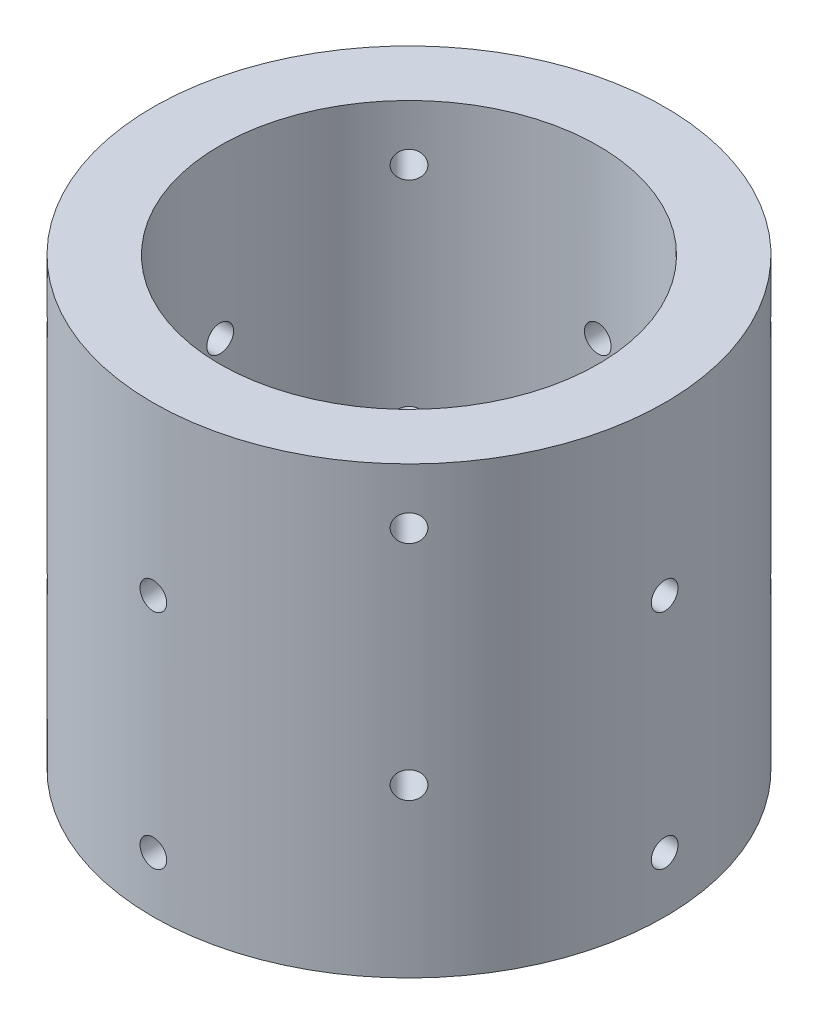
SolidWorks part; units mm, degrees
material "PLA плостность"
ref_plane "Спереди" through (0, 0, 0) normal (0, 0, 1) x (1, 0, 0)
ref_plane "Сверху" through (0, 0, 0) normal (0, 1, 0) x (1, 0, 0)
ref_plane "Справа" through (0, 0, 0) normal (1, 0, 0) x (0, 0, -1)
sketch "Эскиз1" plane through (0, 0, 0) normal (0, 1, 0) x (1, 0, 0)
  circle A0 centre (0, 0) radius 23
  dimension "D1" = 46
extrude "Бобышка-Вытянуть1" add sketch "Эскиз1" along normal blind 10
sketch "Эскиз2" plane through (0, 10, 0) normal (0, 1, 0) x (1, 0, 0)
  circle A0 centre (0, 0) radius 23
  circle A1 centre (0, 0) radius 17
  circle A2 centre (0, 0) radius 23 construction
  dimension "D1" = 34
  dimension "D2" = 0
extrude "Бобышка-Вытянуть2" add sketch "Эскиз2" along normal blind 30
sketch "Эскиз3" plane through (0, 0, 0) normal (1, 0, 0) x (0, 0, -1)
  line L0 (-23, 20) -> (30.2453, 20) construction
  line L1 (-23, 40) -> (-23, 0) construction
  line L2 (0, 25) -> (0, -3.082) construction
  line L3 (17, 40) -> (-17, 40) construction
  line L4 (-23, 0) -> (23, 0) construction
  circle A0 centre (0, 25) radius 1.2
  circle A2 centre (0, 5) radius 1.2
  dimension "D1" = 2.4
  dimension "D3" = 5
  dimension "D4" = 2.4
  dimension "D2" = 15
extrude "Вырез-Вытянуть1" cut sketch "Эскиз3" against normal through all from offset 16.8 offset against normal yes
ref_plane "Плоскость1" through (0, 0, 0) normal (0.7071, 0, 0.7071) x (0, -1, 0)
sketch "Эскиз4" plane through (0, 0, 0) normal (0.7071, 0, 0.7071) x (0, -1, 0)
  line L0 (-20, 23) -> (-20, -29.9249) construction
  line L1 (0, 23) -> (-40, 23) construction
  line L2 (-40, 0) -> (0, 0) construction
  line L3 (0, -23) -> (0, 23) construction
  line L4 (-40, 23) -> (-40, -23) construction
  circle A0 centre (-15, 0) radius 1.2
  circle A2 centre (-35, 0) radius 1.2
  dimension "D1" = 2.4
  dimension "D3" = 2.4
  dimension "D2" = 15
  dimension "D4" = 5
extrude "Вырез-Вытянуть2" cut sketch "Эскиз4" against normal through all
pattern_circular "Круговой массив1" count 4 over 360 about axis through (0, 10, 0) along (0, -1, 0) of "Вырез-Вытянуть1"
pattern_circular "Круговой массив2" count 4 over 360 about axis through (0, 10, 0) along (0, -1, 0) of "Вырез-Вытянуть2"
